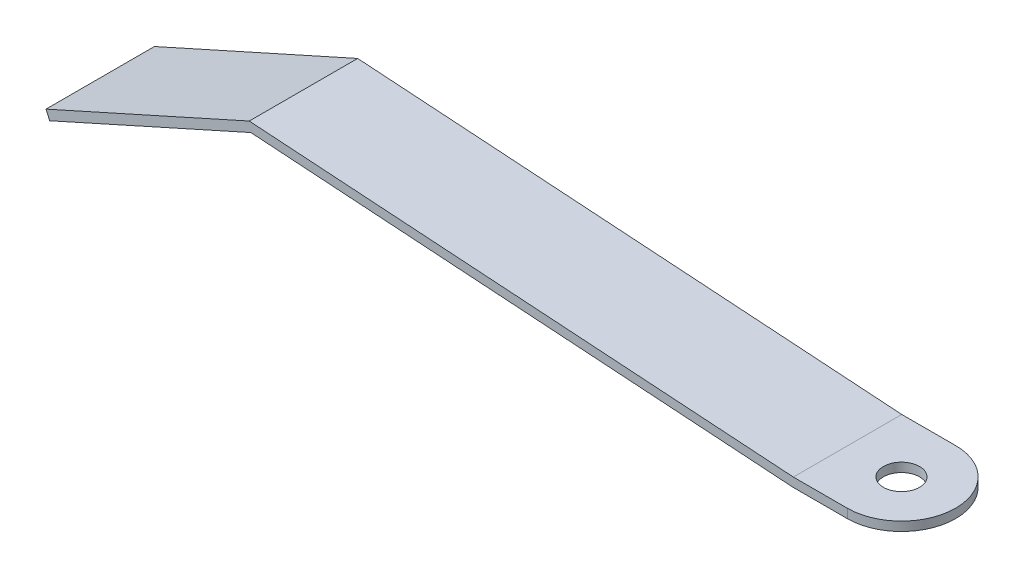
SolidWorks part; units mm, degrees
ref_plane "Front Plane" through (0, 0, 0) normal (0, 0, 1) x (1, 0, 0)
ref_plane "Top Plane" through (0, 0, 0) normal (0, 1, 0) x (1, 0, 0)
ref_plane "Right Plane" through (0, 0, 0) normal (1, 0, 0) x (0, 0, -1)
sketch "Sketch1" plane through (0, 0, 0) normal (0, 0, 1) x (1, 0, 0)
  line L0 (0, 0) -> (-6, 0)
  line L1 (-6, 0) -> (-36, 2)
  line L2 (-36, 2) -> (-47.1328, -3)
  dimension "D1" = 5
  dimension "D2" = 6
  dimension "D3" = 30
  dimension "D4" = 152
  dimension "D5" = 2
extrude "Extrude-Thin1" add sketch "Sketch1" along normal blind 6 thin thin type one direction wall 0.5
fillet "Fillet1" 2 edges at (0, 0.25, 6) (0, 0.25, 0) type full round first side face at (-22.3181, -0.0046, 6) second side face at (-22.3181, -0.0046, 0) middle face at (0, 0.25, 3)
hole_wizard "Ø2.0mm Dowel Hole1" positions "Sketch3" profile "Sketch2" hole size "Ø2.0" standard "ISO" end condition through all
sketch "Sketch3" plane through (0, 0.5, 0) normal (0, 1, 0) x (1, 0, 0)
  arc A1 (-3, -6) -> (-3, 0) centre (-3, -3) ccw construction
  point P0 (-3, -3)
sketch "Sketch2" plane through (-3, 0.5, 3) normal (1, 0, 0) x (0, 0, 1)
  line L0 (0, 0) -> (0, 3.5)
  line L1 (0, 3.5) -> (1, 3.5)
  line L2 (1, 3.5) -> (1, 0)
  line L5 (1, 0) -> (0, 0)
  line L11 (0, -6.35) -> (0, 107.95) construction
  dimension "Thru Hole Dia." = 2
  dimension "Thru Hole Depth" = 3.5
